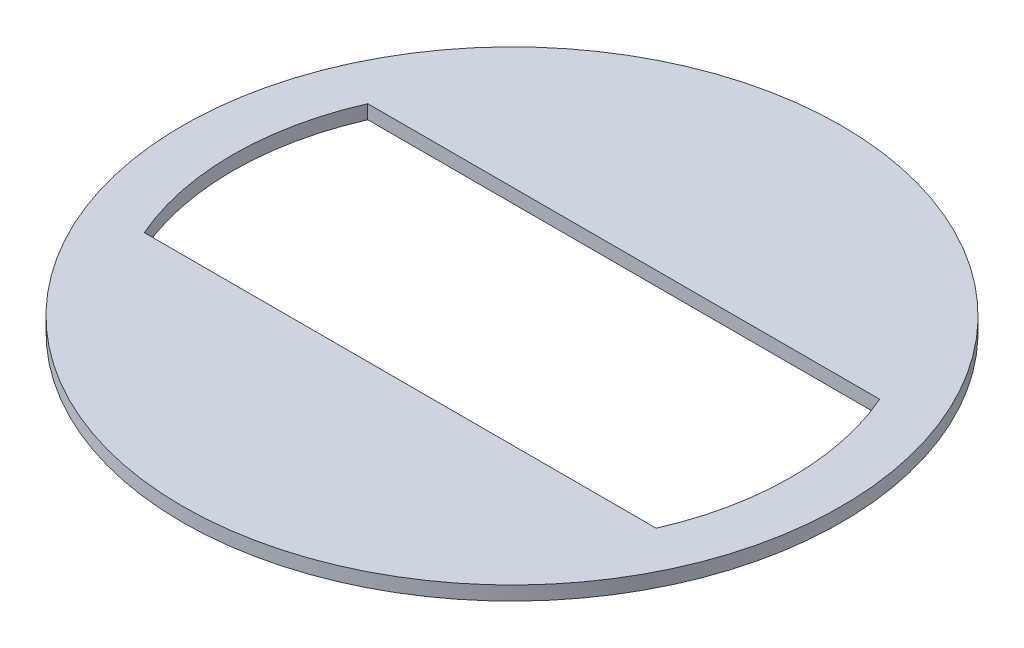
SolidWorks part; units mm, degrees
ref_plane "Front Plane" through (0, 0, 0) normal (0, 0, 1) x (1, 0, 0)
ref_plane "Top Plane" through (0, 0, 0) normal (0, 1, 0) x (1, 0, 0)
ref_plane "Right Plane" through (0, 0, 0) normal (1, 0, 0) x (0, 0, -1)
sketch "Sketch1" plane through (0, 0, 0) normal (0, 1, 0) x (1, 0, 0)
  line L0 (-116.3974, -50.8) -> (116.3974, -50.8)
  line L1 (-116.3974, 50.8) -> (116.3974, 50.8)
  circle A0 centre (0, 0) radius 149.86
  arc A1 (-116.3974, 50.8) -> (-116.3974, -50.8) centre (0, 0) ccw
  arc A2 (116.3974, 50.8) -> (-116.3974, 50.8) centre (0, 0) ccw construction
  arc A3 (-116.3974, -50.8) -> (116.3974, -50.8) centre (0, 0) ccw construction
  arc A4 (116.3974, -50.8) -> (116.3974, 50.8) centre (0, 0) ccw
  dimension "D1" = 299.72
  dimension "D2" = 254
  dimension "D3" = 101.6
extrude "Boss-Extrude1" add sketch "Sketch1" along normal blind 6.35
